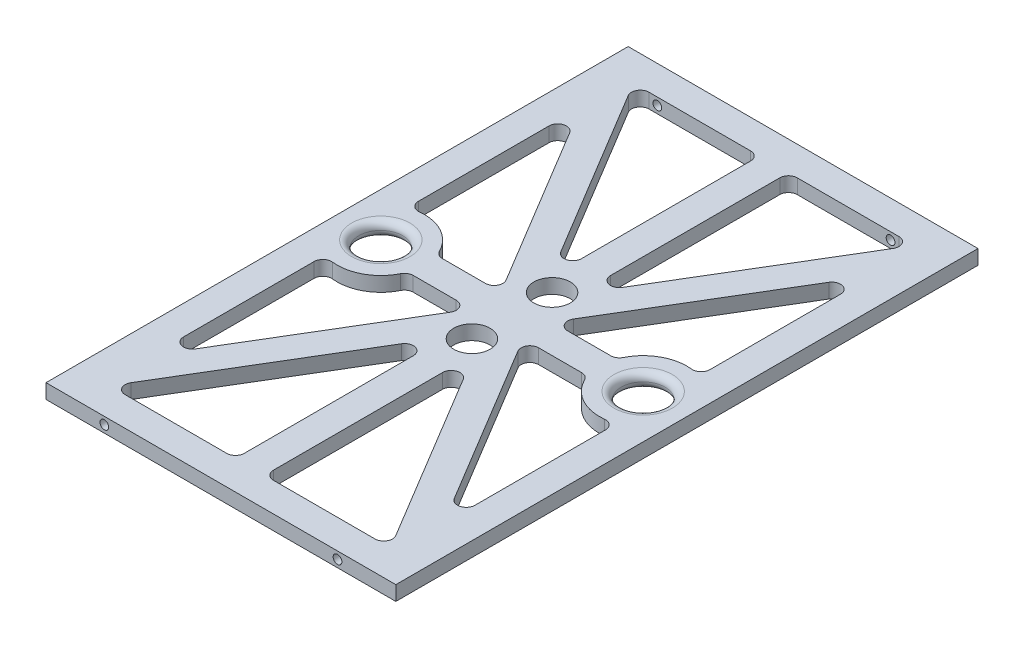
SolidWorks part; units mm, degrees
material "6061-T6 (SS)"
ref_plane "Front Plane" through (0, 0, 0) normal (0, 0, 1) x (1, 0, 0)
ref_plane "Top Plane" through (0, 0, 0) normal (0, 1, 0) x (1, 0, 0)
ref_plane "Right Plane" through (0, 0, 0) normal (1, 0, 0) x (0, 0, -1)
sketch "Sketch1" plane through (0, 0, 0) normal (0, 0, 1) x (1, 0, 0)
  line L1 (0, 0) -> (152.4, 0)
  line L2 (0, 0) -> (0, 6.35)
  line L3 (0, 6.35) -> (152.4, 6.35)
  line L4 (152.4, 0) -> (152.4, 6.35)
  dimension "D2" = 152.4
  dimension "D3" = 6.35
extrude "Boss-Extrude1" add sketch "Sketch1" along normal mid plane 253.619 contours L3 L4 L1 L2
hole_wizard "3/4 (0.75) Diameter Hole1" positions "Sketch2" profile "Sketch3" hole size "3/4" standard "ANSI Inch" end condition through all
sketch "Sketch2" plane through (0, 6.35, 0) normal (0, 1, 0) x (1, 0, 0)
  line L1 (0, -126.8095) -> (0, 126.8095) construction
  line L2 (152.4, -126.8095) -> (152.4, 126.8095) construction
  point P0 (19.05, 0)
  point P2 (133.35, 0)
  point P11 (152.4, 0)
  dimension "D1" = 19.05
  dimension "D2" = 19.05
sketch "Sketch3" plane through (19.05, 6.35, 0) normal (1, 0, 0) x (0, 0, 1)
  line L0 (0, 0) -> (0, 6.35)
  line L1 (0, 6.35) -> (9.525, 6.35)
  line L2 (9.525, 6.35) -> (9.525, 0)
  line L5 (9.525, 0) -> (0, 0)
  line L11 (0, -6.35) -> (0, 107.95) construction
  dimension "Thru Hole Dia." = 19.05
  dimension "Thru Hole Depth" = 6.35
sketch "Sketch4" plane through (0, 6.35, 0) normal (0, 1, 0) x (1, 0, 0)
  line L0 (152.4, 126.8095) -> (0, -126.8095) construction
  line L1 (0, 126.8095) -> (152.4, -126.8095) construction
  line L2 (19.05, 0) -> (133.35, 0) construction
  line L3 (37.0105, -6.35) -> (64.976, -6.35)
  line L4 (12.7, 93.346) -> (64.976, 6.35)
  line L5 (137.3603, 114.1095) -> (82.55, 22.896)
  line L6 (37.0105, 6.35) -> (64.976, 6.35)
  line L7 (15.0397, 114.1095) -> (69.85, 22.896)
  line L8 (139.7, 93.346) -> (87.424, 6.35)
  line L155 (5.4429, 130.0802) -> (157.8429, -123.5388) construction
  line L156 (-5.4429, 123.5388) -> (146.9571, -130.0802) construction
  line L157 (12.7, 93.346) -> (12.7, 17.9605)
  line L158 (139.7, 17.9605) -> (139.7, 93.346)
  line L159 (12.7, -114.1095) -> (139.7, -114.1095)
  line L160 (139.7, -114.1095) -> (139.7, 114.1095)
  line L161 (139.7, 114.1095) -> (12.7, 114.1095)
  line L162 (12.7, 114.1095) -> (12.7, -114.1095)
  line L163 (15.0397, -114.1095) -> (69.85, -114.1095)
  line L164 (139.7, -93.346) -> (139.7, -17.9605)
  line L165 (137.3603, 114.1095) -> (82.55, 114.1095)
  line L167 (146.9571, 130.0802) -> (-5.4429, -123.5388) construction
  line L168 (76.2, 126.8095) -> (76.2, -126.8095) construction
  line L169 (12.7, -17.9605) -> (12.7, -93.346)
  line L170 (0, 126.8095) -> (152.4, 126.8095) construction
  line L171 (19.05, 6.35) -> (133.35, 6.35) construction
  line L172 (64.976, -6.35) -> (12.7, -93.346)
  line L173 (0, -126.8095) -> (152.4, -126.8095) construction
  line L174 (19.05, -6.35) -> (133.35, -6.35) construction
  line L175 (69.85, -22.896) -> (15.0397, -114.1095)
  line L176 (157.8429, 123.5388) -> (5.4429, -130.0802) construction
  line L177 (82.55, -22.896) -> (137.3603, -114.1095)
  line L178 (87.424, -6.35) -> (115.3895, -6.35)
  line L179 (69.85, -22.896) -> (69.85, -114.1095)
  line L180 (87.424, 6.35) -> (115.3895, 6.35)
  line L181 (87.424, -6.35) -> (139.7, -93.346)
  line L182 (82.55, 114.1095) -> (82.55, 22.896)
  line L183 (82.55, -114.1095) -> (137.3603, -114.1095)
  line L184 (82.55, 126.8095) -> (82.55, -126.8095) construction
  line L185 (69.85, 114.1095) -> (15.0397, 114.1095)
  line L186 (82.55, -22.896) -> (82.55, -114.1095)
  line L187 (69.85, 114.1095) -> (69.85, 22.896)
  line L188 (0, -126.8095) -> (0, 126.8095) construction
  arc A45 (12.7, -17.9605) -> (37.0105, -6.35) centre (19.05, 0) ccw
  arc A46 (115.3895, -6.35) -> (139.7, -17.9605) centre (133.35, 0) ccw
  circle A47 centre (133.35, 0) radius 9.525 construction
  arc A48 (139.7, 17.9605) -> (115.3895, 6.35) centre (133.35, 0) ccw
  arc A49 (37.0105, 6.35) -> (12.7, 17.9605) centre (19.05, 0) ccw
  circle A50 centre (19.05, 0) radius 9.525 construction
  dimension "D6" = 19.05
  dimension "D4" = 12.7
  dimension "D5" = 6.35
  dimension "D1" = 6.35
  dimension "D2" = 6.35
  dimension "D7" = 6.35
extrude "Cut-Extrude1" cut sketch "Sketch4" against normal through all
fillet "Fillet1" radius 3.81 28 edges at (64.976, 3.175, 6.35) (139.7, 3.175, 93.346) (15.0397, 3.175, 114.1095) (87.424, 3.175, -6.35) (137.3603, 3.175, -114.1095) (69.85, 3.175, -114.1095) (115.3895, 3.175, 6.35) (139.7, 3.175, 17.9605) (139.7, 3.175, -93.346) (69.85, 3.175, 22.896) (82.55, 3.175, 22.896) (12.7, 3.175, -93.346) (82.55, 3.175, 114.1095) (37.0105, 3.175, -6.35) (12.7, 3.175, -17.9605) (12.7, 3.175, 93.346) (82.55, 3.175, -22.896) (69.85, 3.175, -22.896) (64.976, 3.175, -6.35) (69.85, 3.175, 114.1095) (137.3603, 3.175, 114.1095) (139.7, 3.175, -17.9605) (115.3895, 3.175, -6.35) (12.7, 3.175, 17.9605) (37.0105, 3.175, 6.35) (87.424, 3.175, 6.35) (82.55, 3.175, -114.1095) (15.0397, 3.175, -114.1095)
fillet "Fillet4" radius 3.175 4 edges at (19.05, 0, 9.525) (19.05, 6.35, 9.525) (133.35, 0, 9.525) (133.35, 6.35, 9.525)
hole_wizard "5/8 (0.625) Diameter Hole1" positions "Sketch5" profile "Sketch6" hole size "5/8" standard "ANSI Inch" end condition through all
sketch "Sketch5" plane through (0, 0, 0) normal (0, -1, 0) x (-1, 0, 0)
  line L0 (-19.05, 0) -> (-133.35, 0) construction
  line L1 (-76.2, 126.8095) -> (-76.2, -126.8095) construction
  point P0 (-76.2, 17.4625)
  point P2 (-76.2, -17.4625)
  dimension "D1" = 34.925
  dimension "D2" = 17.4625
sketch "Sketch6" plane through (76.2, 0, -17.4625) normal (1, 0, 0) x (0, 0, -1)
  line L0 (0, 0) -> (0, 6.35)
  line L1 (0, 6.35) -> (7.9375, 6.35)
  line L2 (7.9375, 6.35) -> (7.9375, 0)
  line L5 (7.9375, 0) -> (0, 0)
  line L11 (0, -6.35) -> (0, 107.95) construction
  dimension "Thru Hole Dia." = 15.875
  dimension "Thru Hole Depth" = 6.35
hole_wizard "#10-24 Tapped Hole1" positions "Sketch7" profile "Sketch9" tap size "#10-24" standard "ANSI Inch"
sketch "Sketch7" plane through (0, 0, 126.8095) normal (0, 0, 1) x (1, 0, 0)
  line L0 (0, 0) -> (0, 6.35) construction
  point P0 (127, 3.175)
  point P2 (25.4, 3.175)
  point P10 (0, 3.175)
  dimension "D1" = 25.4
  dimension "D2" = 101.6
cosmetic thread "Hole Thread1" parameters "D1"=9.652, "D2"=4.826
cosmetic thread "Hole Thread2" parameters "D1"=9.652, "D2"=4.826
sketch "Sketch9" plane through (127, 3.175, 126.8095) normal (1, 0, 0) x (0, -1, 0)
  line L0 (0, 0) -> (0, 20.1908)
  line L1 (0, 20.1908) -> (1.8986, 19.05)
  line L2 (1.8986, 19.05) -> (1.8986, 0)
  line L5 (1.8986, 0) -> (0, 0)
  line L10 (0, 20.1908) -> (-1.8987, 19.05) construction
  line L11 (0, -6.35) -> (0, 107.95) construction
  dimension "Tap Drill Dia." = 3.7973
  dimension "Tap Drill Depth" = 19.05
  dimension "Drill Angle" = 118
hole_wizard "#10-24 Tapped Hole2" positions "Sketch10" profile "Sketch11" tap size "#10-24" standard "ANSI Inch"
sketch "Sketch10" plane through (0, 0, -126.8095) normal (0, 0, -1) x (-1, 0, 0)
  line L0 (0, 0) -> (0, 6.35) construction
  point P0 (-25.4, 3.175)
  point P2 (-127, 3.175)
  point P7 (0, 3.175)
  dimension "D1" = 25.4
  dimension "D2" = 101.6
sketch "Sketch11" plane through (25.4, 3.175, -126.8095) normal (1, 0, 0) x (0, 1, 0)
  line L0 (0, 0) -> (0, 20.1908)
  line L1 (0, 20.1908) -> (1.8986, 19.05)
  line L2 (1.8986, 19.05) -> (1.8986, 0)
  line L5 (1.8986, 0) -> (0, 0)
  line L10 (0, 20.1908) -> (-1.8986, 19.05) construction
  line L11 (0, -6.35) -> (0, 107.95) construction
  dimension "Tap Drill Dia." = 3.7973
  dimension "Tap Drill Depth" = 19.05
  dimension "Drill Angle" = 118
cosmetic thread "Hole Thread3" parameters "D1"=9.652, "D2"=4.826
cosmetic thread "Hole Thread4" parameters "D1"=9.652, "D2"=4.826
equation "\"D2@Sketch2\"=\"D1@Sketch2\""
equation "\"D4@Sketch4\"=\"D3@Sketch4\""
equation "\"D5@Sketch4\"=\"D7@Sketch4\""
equation "\"D2@Sketch5\"=\"D1@Sketch5\"/2"
